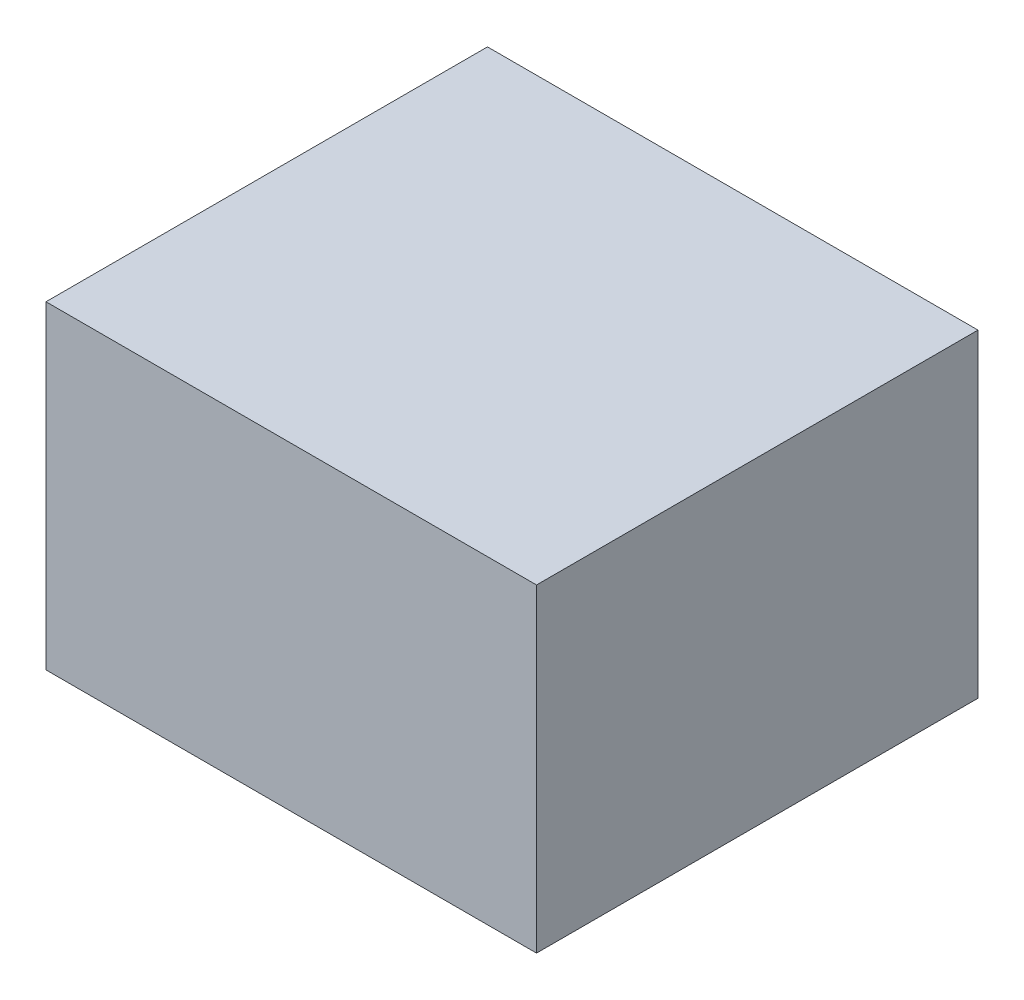
SolidWorks part; units mm, degrees
ref_plane "Front Plane" through (0, 0, 0) normal (0, 0, 1) x (1, 0, 0)
ref_plane "Top Plane" through (0, 0, 0) normal (0, 1, 0) x (1, 0, 0)
ref_plane "Right Plane" through (0, 0, 0) normal (1, 0, 0) x (0, 0, -1)
sketch "Sketch1" plane through (0, 50, 0) normal (0, 1, 0) x (1, 0, 0)
  line L1 (-247.0345, 875.5294) -> (-47.0345, 875.5294)
  line L2 (-247.0345, 875.5294) -> (-247.0345, 1055.5294)
  line L3 (-247.0345, 1055.5294) -> (-47.0345, 1055.5294)
  line L4 (-47.0345, 875.5294) -> (-47.0345, 1055.5294)
  line L5 (-247.0345, 875.5294) -> (-47.0345, 1055.5294) construction
  line L6 (-247.0345, 1055.5294) -> (-47.0345, 875.5294) construction
  point P0 (-147.0345, 965.5294)
  point P6 (0, 0)
  point P7 (116.038, 943.0457)
  point P8 (-147.0345, 965.5294)
  dimension "D1" = 180
  dimension "D2" = 200
extrude "Boss-Extrude1" add sketch "Sketch1" along normal blind 130
